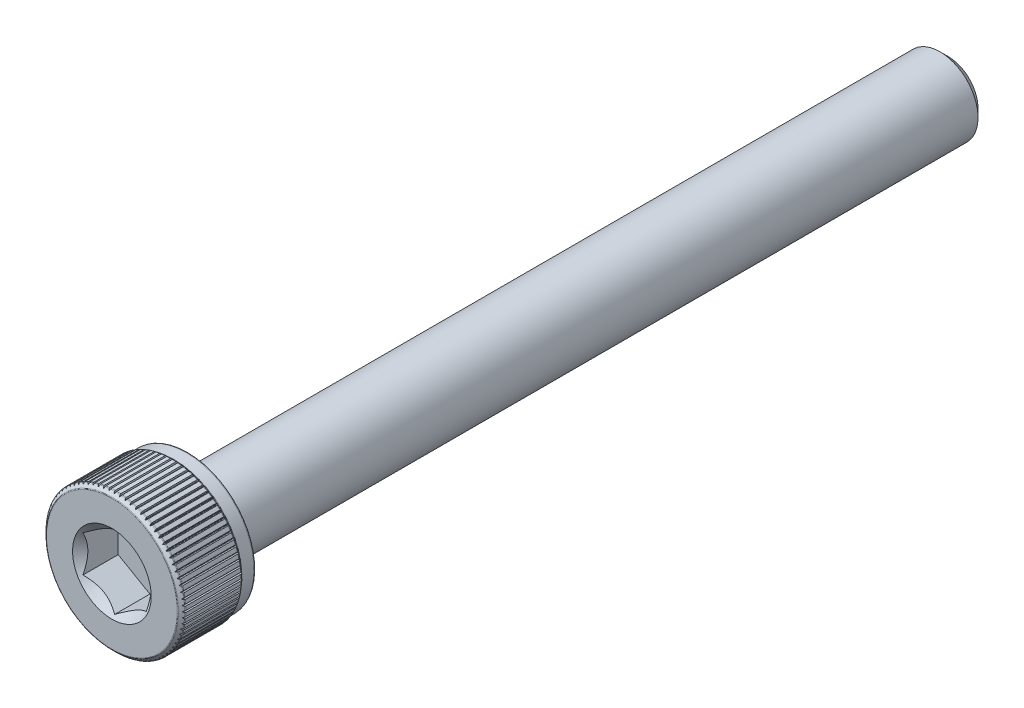
SolidWorks part; units mm, degrees
ref_plane "Front Plane" through (0, 0, 0) normal (0, 0, 1) x (1, 0, 0)
ref_plane "Top Plane" through (0, 0, 0) normal (0, 1, 0) x (1, 0, 0)
ref_plane "Right Plane" through (0, 0, 0) normal (1, 0, 0) x (0, 0, -1)
sketch "Sketch1" plane through (0, 0, 0) normal (1, 0, 0) x (0, 0, -1)
  line L0 (-16.5, 0) -> (16.5, 0) construction
  line L1 (16.5, 0) -> (16.5, 1.1752) construction
  line L2 (16.5, 1.1752) -> (16.1752, 1.5) construction
  line L3 (16.1752, 1.5) -> (16.125, 1.5) construction
  line L4 (16.125, 1.5) -> (-13.5, 1.5) construction
  line L5 (-13.5, 1.5) -> (-13.5, 2.75) construction
  line L6 (-13.5, 2.75) -> (-16.5, 2.75) construction
  line L7 (-16.5, 2.75) -> (-16.5, 0) construction
  line L8 (16.5, 1.1752) -> (16.5, 1.5) construction
  line L9 (16.4688, 1.5541) -> (16.7188, 1.1211) construction
  line L10 (16.7188, 1.1211) -> (16.9687, 1.5541) construction
  line L11 (16.9687, 1.5541) -> (16.4688, 1.5541) construction
  line L12 (16.7188, 1.5541) -> (16.7187, 1.5) construction
  line L13 (16.7188, 1.1211) -> (16.7188, 1.1752) construction
  line L14 (16.6875, 1.1752) -> (16.75, 1.1752) construction
  line L15 (16.5, 1.5) -> (16.9375, 1.5) construction
  line L16 (16.4844, 1.5271) -> (16.9531, 1.5271) construction
  line L17 (16.5, 0) -> (16.5, -1.5) construction
  line L18 (-13.65, 2.75) -> (-13.5, 2.6) construction
  line L19 (-16.35, 2.75) -> (-16.5, 2.6) construction
  line L20 (-13.5, 1.5) -> (-13.5, 0) construction
  line L21 (-13.5, 0.75) -> (-3.5, 0.75) construction
  line L22 (-3.5, 0.75) -> (6.5, 0.75) construction
  line L23 (6.5, 0.75) -> (16.5, 0.75) construction
  line L24 (-3.5, 0.75) -> (-3.5, 1.5) construction
  line L25 (-3.5, 1.5) -> (-3.5, 2.75) construction
  line L26 (6.5, 0.75) -> (6.5, 2.75) construction
  point P0 (-16.5, 1.25)
  point P3 (15.25, 1.5)
  point P4 (0, 0)
  point P18 (6.5, 1.5)
  point P22 (16.7188, 1.1752)
  point P24 (16.125, 1.5)
  point P25 (16.7187, 1.5)
  point P28 (16.7187, 1.5271)
  point P29 (15.25, -1.5)
  point P30 (-3.5, 1.5)
  point P31 (-15, 2.75)
  point P37 (-14.025, 2.75)
  point P38 (-16.275, 2.75)
  point P45 (-3.5, 0.75)
  point P46 (6.5, 0.75)
  dimension "D1" = 45
  dimension "D2" = 0.0625
  dimension "D7" = 0.15
  dimension "D8" = 0.15
  dimension "D9" = 0.15
  dimension "D10" = 0.075
  dimension "D11" = 0.375
  dimension "Drive Size" = 2.5
  dimension "Head Diameter" = 5.5
  dimension "Head Height" = 3
  dimension "Thread Pitch" = 0.5
  dimension "Thread Dia" = 3
  dimension "Length" = 30
  dimension "D12" = 0.375
  dimension "D4" = 1.25
  dimension "Key Engagement" = 1.5
sketch "Sketch2" plane through (0, 0, 0) normal (1, 0, 0) x (0, 0, -1)
  line L0 (-16.5, 0) -> (-16.5, 2.5806)
  line L1 (-16.3306, 2.75) -> (-14.1569, 2.75)
  line L2 (-13.5, 2.6062) -> (-13.5, 1.65)
  line L4 (16.1752, 1.5) -> (16.5, 1.1752)
  line L5 (16.5, 1.1752) -> (16.5, 0)
  line L6 (-13.5, 2.75) -> (-16.5, 2.75) construction
  line L7 (16.5, 0) -> (-16.5, 0)
  line L8 (-16.35, 2.75) -> (-16.5, 2.6) construction
  line L10 (-16.3637, 2.7363) -> (-16.4863, 2.6137)
  line L12 (-14.0431, 2.675) -> (-13.5688, 2.675)
  line L14 (-13.65, 2.75) -> (-13.5, 2.6) construction
  line L15 (-14.1238, 2.7363) -> (-14.0762, 2.6887)
  line L17 (-13.5, 1.5) -> (-13.5, 2.75) construction
  line L19 (-13.35, 1.5) -> (16.1752, 1.5)
  line L20 (16.125, 1.5) -> (-13.5, 1.5) construction
  arc A0 (-13.5688, 2.675) -> (-13.5, 2.6062) centre (-13.5688, 2.6062) cw
  arc A1 (-13.5, 1.65) -> (-13.35, 1.5) centre (-13.35, 1.65) ccw
  arc A2 (-16.3637, 2.7363) -> (-16.3306, 2.75) centre (-16.3306, 2.7031) cw
  arc A3 (-16.4863, 2.6137) -> (-16.5, 2.5806) centre (-16.4531, 2.5806) ccw
  arc A4 (-14.1238, 2.7363) -> (-14.1569, 2.75) centre (-14.1569, 2.7031) ccw
  arc A5 (-14.0762, 2.6887) -> (-14.0431, 2.675) centre (-14.0431, 2.7219) ccw
  point P22 (-13.575, 2.675)
  point P37 (-14.0625, 2.675)
  dimension "D2" = 0.0688
  dimension "D3" = 0.15
  dimension "D4" = 0.0469
  dimension "D1" = 0.5625
revolve "Revolve1" add sketch "Sketch2" angle 360 about L7
sketch "Sketch3" plane through (0, 0, 16.5) normal (0, 0, 1) x (1, 0, 0)
  line L1 (1.25, -0.7217) -> (1.25, 0.7217)
  line L2 (1.25, 0.7217) -> (0, 1.4434)
  line L3 (0, 1.4434) -> (-1.25, 0.7217)
  line L4 (-1.25, 0.7217) -> (-1.25, -0.7217)
  line L5 (-1.25, -0.7217) -> (0, -1.4434)
  line L6 (0, -1.4434) -> (1.25, -0.7217)
  circle A0 centre (0, 0) radius 1.25 construction
  circle A1 centre (0, 0) radius 2.75 construction
  circle A2 centre (0, 0) radius 2.75 construction
  circle A3 centre (0, 0) radius 1.4434 construction
  dimension "D1" = 2.8868
extrude "Cut-Extrude1" cut sketch "Sketch3" against normal up to vertex (1.5 mm away) up to point (0, 2.75, 15)
sketch "Sketch4" plane through (0, 0, 16.5) normal (0, 0, 1) x (1, 0, 0)
  circle A0 centre (0, 0) radius 1.5516
  dimension "D1" = 3.1033
extrude "Cut-Extrude2" cut sketch "Sketch4" against normal up to vertex (1.5 mm away) draft 45 up to point (0, 2.75, 15)
sketch "Sketch6" plane through (0, 0, -16.5) normal (0, 0, -1) x (-1, 0, 0)
  circle A0 centre (0, 0) radius 1.5
curve "Helix/Spiral1" pitch 0.5 height 30.5 turns 61
sketch "Sketch7" plane through (0, 0, 0) normal (1, 0, 0) x (0, 0, -1)
  line L0 (16.4844, 1.5271) -> (16.9531, 1.5271)
  line L1 (16.9531, 1.5271) -> (16.75, 1.1752)
  line L2 (16.75, 1.1752) -> (16.6875, 1.1752)
  line L3 (16.6875, 1.1752) -> (16.4844, 1.5271)
sweep "Cut-Sweep1" [suppressed] cut profiles "Sketch7" path "Helix/Spiral1"
sketch "Sketch8" plane through (0, 0, 0) normal (1, 0, 0) x (0, 0, -1)
  line L0 (-15, 0) -> (-15, 1.65)
  line L1 (-15, 0.7217) -> (-15, 1.4434) construction
  line L2 (-13.35, 1.5) -> (-13.25, 1.5)
  line L3 (-13.5, 1.65) -> (-15, 1.65)
  line L4 (-13.25, 1.5) -> (-12.384, 0)
  line L5 (-12.384, 0) -> (-15, 0)
  line L7 (-16.5, 0) -> (16.5, 0) construction
  line L8 (-13.5, 1.5) -> (-13.5, 2.75) construction
  arc A0 (-13.5, 1.65) -> (-13.35, 1.5) centre (-13.35, 1.65) ccw construction
  arc A1 (-13.5, 1.65) -> (-13.35, 1.5) centre (-13.35, 1.65) ccw
  dimension "D1" = 60
  dimension "D2" = 0.25
revolve "Revolve2" add sketch "Sketch8" angle 360 about L5
sketch "Sketch9" plane through (0, 0, 16.5) normal (0, 0, 1) x (1, 0, 0)
  line L0 (-0.0125, 2.703) -> (-0.0687, 2.8285)
  line L1 (-0.0687, 2.8285) -> (0.0688, 2.8285)
  line L2 (0.0688, 2.8285) -> (0.0125, 2.703)
  line L3 (0, 2.75) -> (0, 2.6) construction
  line L4 (0, 0) -> (-0.0687, 2.8285) construction
  line L5 (0.0688, 2.8285) -> (0, 0) construction
  circle A0 centre (0, 0) radius 2.675 construction
  arc A4 (-0.0125, 2.703) -> (0.0125, 2.703) centre (0, 2.7086) ccw
  point P10 (0, 2.675)
  point P19 (0, 2.675)
  dimension "D2" = 0.0138
  dimension "D1" = 0.1375
  dimension "D3" = 2.785
extrude "Cut-Extrude3" cut sketch "Sketch9" against normal through all
pattern_circular "CirPattern1" count 80 over 360 about axis through (0, 0, 16.3306) along (0, 0, -1) of "Cut-Extrude3"
equation "\"D2@Sketch1\" = \"Thread Pitch@Sketch1\" / 8"
equation "\"D4@Helix/Spiral1\" = \"Thread Pitch@Sketch1\""
equation "\"D7@Sketch1\" = \"Head Height@Sketch1\" * .05"
equation "\"D8@Sketch1\"=\"D7@Sketch1\""
equation "\"D9@Sketch1\"=\"D7@Sketch1\""
equation "\"D10@Sketch1\"=\"D7@Sketch1\"/2"
equation "\"D11@Sketch1\"=\"D10@Sketch1\"*5"
equation "\"D4@Sketch1\"=\"Thread Pitch@Sketch1\"*2.5"
equation "\"D12@Sketch1\"=\"Thread Pitch@Sketch1\"*.75"
equation "\"D3@Helix/Spiral1\"=\"Length@Sketch1\"+\"Thread Pitch@Sketch1\""
equation "\"D1@Sketch2\"=\"Head Height@Sketch1\"*0.1875"
equation "\"D2@Sketch2\"=\"Head Diameter@Sketch1\"*0.0125"
equation "\"D3@Sketch2\"=\"Thread Dia@Sketch1\"*0.05"
equation "\"D1@Sketch9\"=\"Head Diameter@Sketch1\"*0.025"
equation "\"D2@Sketch9\"=\"D1@Sketch9\"*0.1"
equation "\"D2@Sketch8\"=\"Thread Pitch@Sketch1\"*00.5"
equation "\"D4@Sketch2\"=\"D8@Sketch1\"*0.3125"
equation "\"D1@CirPattern1\"=int ((360/\"D3@Sketch9\")*0.625)"
equation "\"D1@Sketch4\"=\"D1@Sketch3\" * 01.075"
